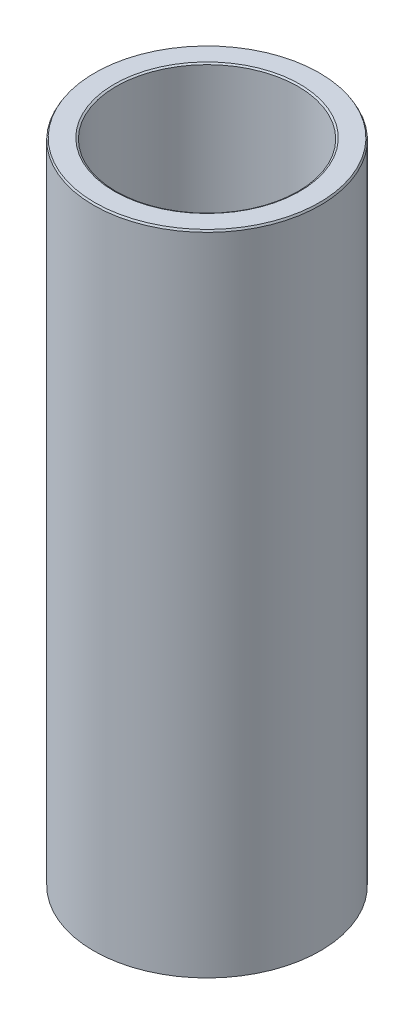
SolidWorks part; units mm, degrees
ref_plane "Front Plane" through (0, 0, 0) normal (0, 0, 1) x (1, 0, 0)
ref_plane "Top Plane" through (0, 0, 0) normal (0, 1, 0) x (1, 0, 0)
ref_plane "Right Plane" through (0, 0, 0) normal (1, 0, 0) x (0, 0, -1)
sketch "Sketch1" plane through (0, 0, 0) normal (0, 1, 0) x (1, 0, 0)
  circle A0 centre (0, 0) radius 40
  dimension "SLEEVE_OD" = 80
extrude "Boss-Extrude1" add sketch "Sketch1" along normal blind 228.7769
sketch "Sketch2" plane through (0, 0, 0) normal (0, 1, 0) x (1, 0, 0)
  circle A0 centre (0, 0) radius 32.0959
  dimension "BORE_D" = 64.1919
extrude "Cut-Extrude1" cut sketch "Sketch2" along normal through all
chamfer "Chamfer1" distance 0.6411 angle 30 4 edges at (0, 228.7769, 32.0959) (0, 0, 32.0959) (0, 0, 40) (0, 228.7769, 40) first distance on face at (0, 228.7769, 32.0959) first distance on face at (0, 0, 32.0959) first distance on face at (0, 228.7769, 40)
